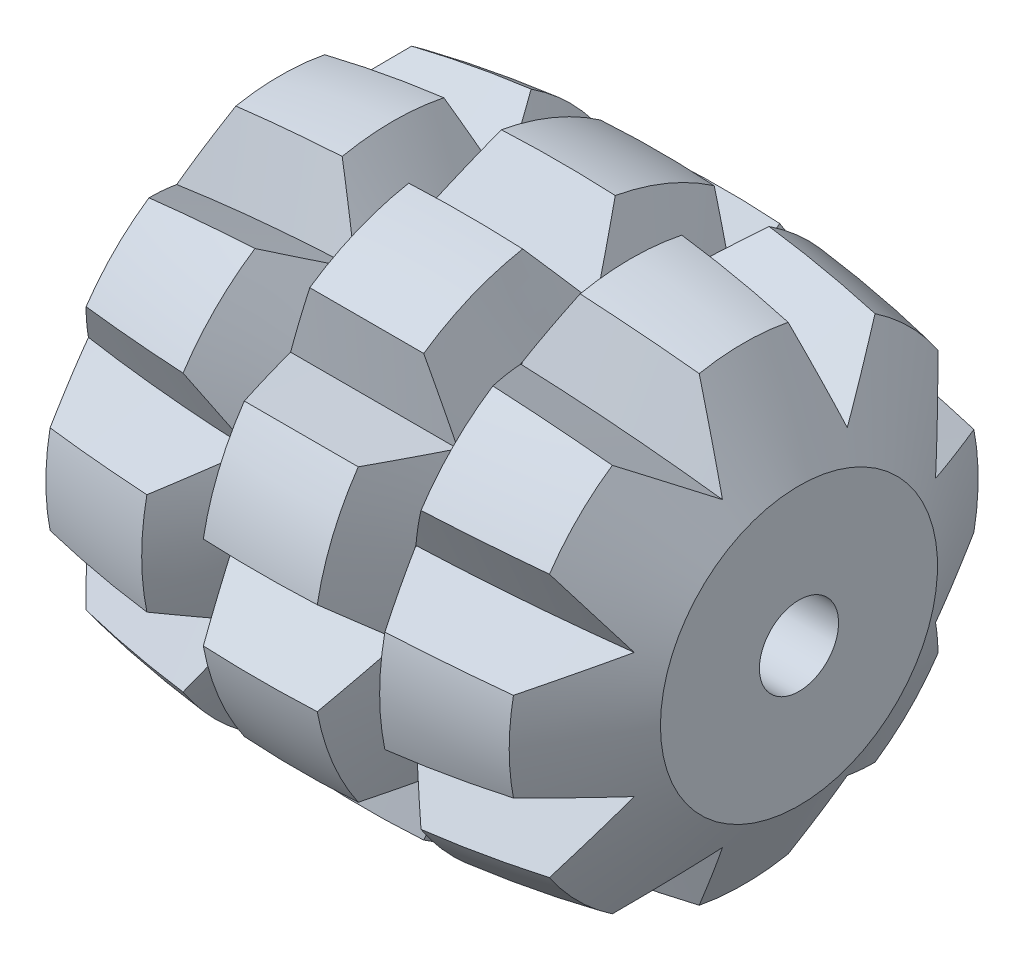
SolidWorks part; units mm, degrees
note: '?' marks a value the reader was unsure of.
material "橡胶"
ref_plane "前视基准面" through (0, 0, 0) normal (0, 0, 1) x (1, 0, 0)
ref_plane "上视基准面" through (0, 0, 0) normal (0, 1, 0) x (1, 0, 0)
ref_plane "右视基准面" through (0, 0, 0) normal (1, 0, 0) x (0, 0, -1)
sketch "草图1" plane through (0, 0, 0) normal (0, 0, 1) x (1, 0, 0)
  line L0 (0, 0) -> (0, 71.3997) construction
  line L1 (0, 0) -> (14.4328, 72.5584) construction
  line L2 (0, 0) -> (-14.4328, 72.5584) construction
  line L3 (0, 60) -> (20.4052, 60) construction
  line L4 (-35.0513, 47) -> (41.6515, 47) construction
  line L5 (-14.5, 54) -> (-11.7054, 58.8471)
  line L6 (-14.5, 47) -> (14.5, 47) construction
  line L7 (-14.5, 49) -> (-14.5, 54)
  line L8 (-14.5, 54) -> (14.5, 54) construction
  line L9 (14.5, 49) -> (14.5, 54)
  line L10 (14.5, 54) -> (11.7054, 58.8471)
  line L11 (-14.5, 49) -> (14.5, 49) construction
  line L12 (-14.5, 47) -> (14.5, 47) construction
  line L13 (-2.8787, 59.9309) -> (2.8787, 59.9309) construction
  line L14 (-2.8787, 59.9309) -> (0, 0) construction
  line L15 (0, 0) -> (2.8787, 59.9309) construction
  line L16 (0, 0) -> (-8.967, 89.0513) construction
  line L17 (0, 0) -> (9.8394, 97.7152) construction
  line L18 (-6.0113, 59.6981) -> (-4.2242, 56.8433)
  line L19 (-4.2242, 56.8433) -> (-2.8787, 59.9309)
  line L20 (2.8787, 59.9309) -> (4.2242, 56.8433)
  line L21 (4.2242, 56.8433) -> (6.0113, 59.6981)
  line L22 (0, 0) -> (-4.2242, 56.8433) construction
  line L23 (4.2242, 56.8433) -> (0, 0) construction
  line L24 (-14.5, 49) -> (14.5, 49)
  line L25 (-14.5, 49) -> (-14.5, 47) construction
  line L26 (14.5, 47) -> (14.5, 49) construction
  arc A0 (11.7054, 58.8471) -> (6.0113, 59.6981) centre (0, 0) ccw
  circle A1 centre (0, 0) radius 57 construction
  arc A2 (-6.0113, 59.6981) -> (-11.7054, 58.8471) centre (0, 0) ccw
  arc A3 (2.8787, 59.9309) -> (-2.8787, 59.9309) centre (0, 0) ccw
  dimension "D1" = 120
  dimension "D10" = 114
  dimension "D2" = 11.25
  dimension "D3" = 13
  dimension "D4" = 29
  dimension "D5" = 7
  dimension "D6" = 2
  dimension "D7" = 5.5
  dimension "D8" = 5.5
  dimension "D9" = 5.5
  dimension "D11" = 4.25
revolve "旋转1" add sketch "草图1" angle 360 about L4
ref_plane "基准面1" through (0, 0, 0) normal (-1, 0, 0) x (0, 0, 1)
sketch "草图2" plane through (0, 0, 0) normal (-1, 0, 0) x (0, 0, 1)
  line L0 (0, 0) -> (0, 128.5789) construction
  line L1 (0, 57) -> (3.6607, 57) construction
  line L2 (0, 57) -> (3.6005, 61.291)
  line L3 (0, 57) -> (-3.6005, 61.291)
  line L4 (-3.6005, 61.291) -> (3.6005, 61.291)
  line L5 (0, 0) -> (51.1498, 0) construction
  circle A0 centre (0, 47) radius 10 construction
  dimension "D1" = 20
  dimension "D2" = 80
revolve "切除-旋转1" cut sketch "草图2" angle 8.5 mid plane about L5
ref_axis "基准轴1" through (-43.0992, 47, 0) along (1, 0, 0)
pattern_circular "阵列(圆周)1" count 8 over 360 about axis through (-43.0992, 47, 0) along (1, 0, 0) of "切除-旋转1"
sketch "草图3" plane through (0, 0, 0) normal (-1, 0, 0) x (0, 0, 1)
  line L0 (0, 0) -> (70.9679, 0) construction
ref_axis "基准轴2" through (0, 0, 83.3578) along (0, 0, -1)?
sketch "草图6" plane through (0, 0, 0) normal (-1, 0, 0) x (0, 0, 1)
  line L0 (0, 47) -> (4.9484, 58.9466) construction
  line L1 (0, 47) -> (0, 60.5869) construction
  line L2 (0, 0) -> (0, 72.5584) construction
  line L3 (0, 47) -> (-23.0388, -8.6207) construction
  line L4 (-18.0126, 3.5138) -> (26.2772, -14.8316) construction
  arc A0 (7.3391, 57.6464) -> (2.3386, 59.7177) centre (0, 47) ccw construction
  circle A1 centre (-18.0126, 3.5138) radius 60 construction
  dimension "D2" = 120
  dimension "D1" = 22.5
ref_plane "基准面7" through (-0.2695, -0.0185, -0.0077) normal (-0.9973, -0.0685, -0.0284) x (-0.0283, -0.0019, 0.9996)
sketch "草图7" plane through (-0.2695, -0.0185, -0.0077) normal (-0.9973, -0.0685, -0.0284) x (-0.0283, -0.0019, 0.9996)
  line L0 (3.7496, 56.1879) -> (9.6571, 59.2705)
  line L1 (-0.0913, 46.8896) -> (4.8319, 58.8082) construction
  line L2 (9.6571, 59.2705) -> (1.7397, 62.541)
  line L3 (1.7397, 62.541) -> (3.7496, 56.1879)
  line L4 (-18.0121, 3.5056) -> (11.6193, 75.2394) construction
  line L5 (1.1281, 49.8417) -> (-0.5016, 45.8964) construction
  circle A0 centre (-18.0121, 3.5056) radius 57 construction
  dimension "D1" = 114
  dimension "D2" = 80
revolve "切除-旋转2" cut sketch "草图7" angle 11 about L4
pattern_circular "阵列(圆周)2" count 8 over 360 about axis through (0, 47, 0) along (1, 0, 0) of "切除-旋转2"
mirror "镜向1" about plane through (0, 0, 0) normal (-1, 0, 0) of "阵列(圆周)2", "切除-旋转2"
